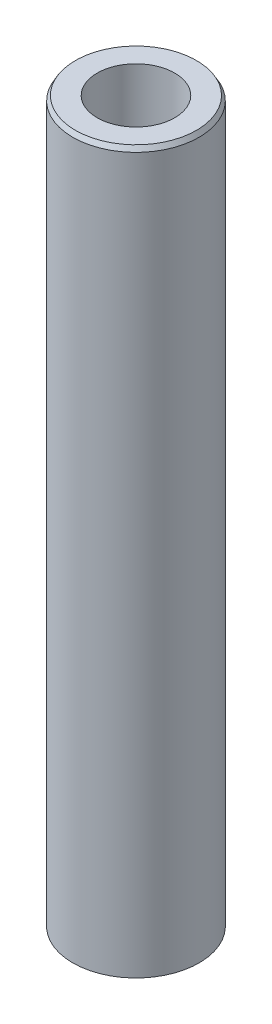
SolidWorks part; units mm, degrees
ref_plane "Front Plane" through (0, 0, 0) normal (0, 0, 1) x (1, 0, 0)
ref_plane "Top Plane" through (0, 0, 0) normal (0, 1, 0) x (1, 0, 0)
ref_plane "Right Plane" through (0, 0, 0) normal (1, 0, 0) x (0, 0, -1)
sketch "Sketch1" plane through (0, 0, 0) normal (0, 1, 0) x (1, 0, 0)
  circle A0 centre (0, 0) radius 52.5
  dimension "SHAFT_OD" = 105
extrude "Boss-Extrude1" add sketch "Sketch1" along normal blind 600
sketch "Sketch2" plane through (0, 0, 0) normal (0, 1, 0) x (1, 0, 0)
  circle A0 centre (0, 0) radius 32.1978
  dimension "BORE_D" = 64.3956
extrude "Cut-Extrude1" cut sketch "Sketch2" along normal through all
chamfer "Chamfer1" distance 3.8648 angle 30 2 edges at (0, 600, 52.5) (0, 0, 52.5) first distance on face at (0, 600, 52.5) first distance on face at (0, 0, 32.1978)
